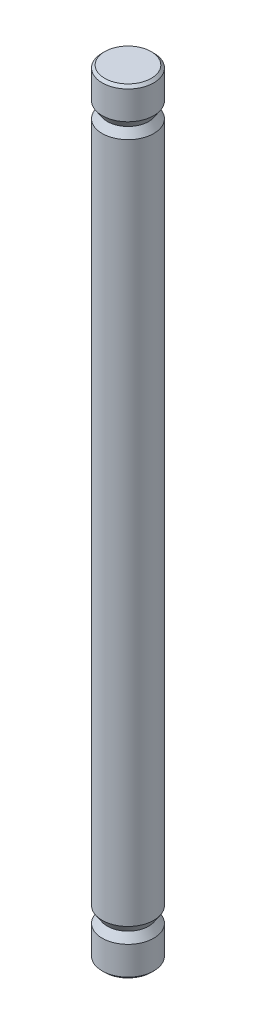
SolidWorks part; units mm, degrees
ref_plane "Plan de face" through (0, 0, 0) normal (0, 0, 1) x (1, 0, 0)
ref_plane "Plan de dessus" through (0, 0, 0) normal (0, 1, 0) x (1, 0, 0)
ref_plane "Plan de droite" through (0, 0, 0) normal (1, 0, 0) x (0, 0, -1)
sketch "Esquisse1" plane through (0, 0, 0) normal (0, 1, 0) x (1, 0, 0)
  circle A0 centre (0, 0) radius 2.5
  dimension "D1" = 5
extrude "Boss.-Extru.1" add sketch "Esquisse1" along normal blind 75
chamfer "Chanfrein1" distance 0.25 angle 45 2 edges at (0, 0, 2.5) (0, 75, 2.5)
ref_axis "Axe1" through (0, 74.75, 0) along (0, -1, 0)
sketch "Esquisse2" plane through (0, 0, 0) normal (0, 0, 1) x (1, 0, 0)
  line L0 (2.5, 72) -> (2, 71.25)
  line L1 (2.5, 0.25) -> (2.5, 74.75) construction
  line L2 (2, 71.25) -> (2.5, 70.5)
  line L3 (2.25, 75) -> (-2.25, 75) construction
  line L4 (2.5, 72) -> (2.5, 70.5)
  line L5 (2.5, 37.5) -> (-2.5, 37.5) construction
  line L6 (-2.5, 74.75) -> (-2.5, 0.25) construction
  line L7 (2, 3.75) -> (2.5, 4.5)
  line L8 (2.5, 3) -> (2, 3.75)
  line L9 (2.5, 3) -> (2.5, 4.5)
  dimension "D1" = 3
  dimension "D2" = 0.5
  dimension "D3" = 1.5
revolve "Enlèvement de matière-Révolution1" cut sketch "Esquisse2" angle 360 about axis through (0, 74.75, 0) along (0, -1, 0)
